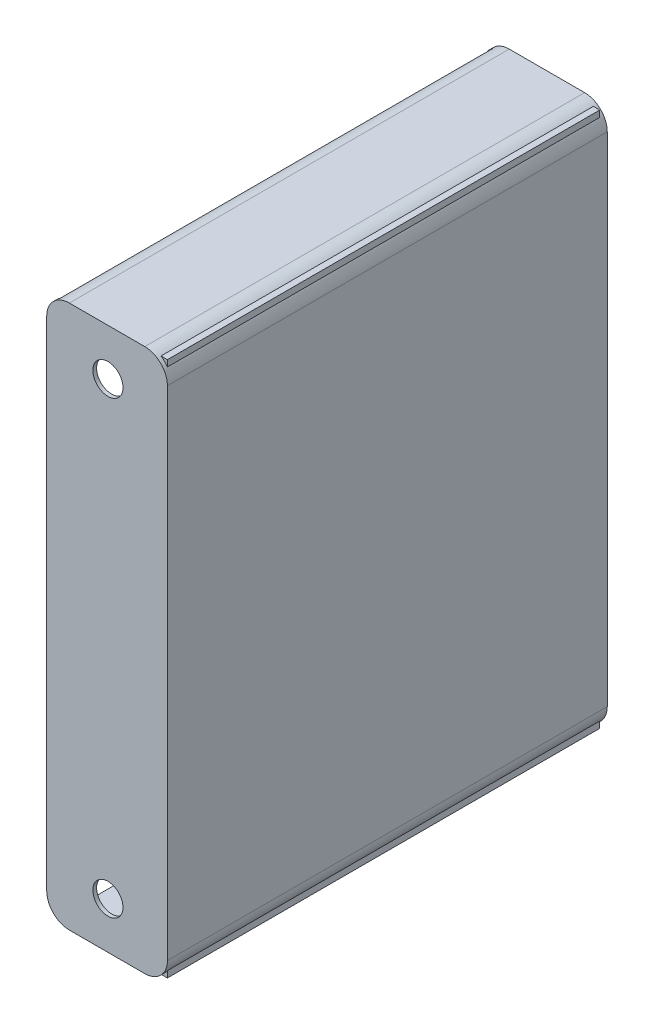
SolidWorks part; units mm, degrees
material "Hexcel AS4C (3000 Filaments)"
ref_plane "Front Plane" through (0, 0, 0) normal (0, 0, 1) x (1, 0, 0)
ref_plane "Top Plane" through (0, 0, 0) normal (0, 1, 0) x (1, 0, 0)
ref_plane "Right Plane" through (0, 0, 0) normal (1, 0, 0) x (0, 0, -1)
sketch "Sketch1" plane through (0, 0, 0) normal (1, 0, 0) x (0, 0, -1)
  line L1 (370.332, -457.2) -> (-370.332, -457.2)
  line L2 (370.332, -457.2) -> (370.332, 457.2)
  line L3 (370.332, 457.2) -> (-370.332, 457.2)
  line L4 (-370.332, -457.2) -> (-370.332, 457.2)
  line L5 (370.332, -457.2) -> (-370.332, 457.2) construction
  line L6 (370.332, 457.2) -> (-370.332, -457.2) construction
  point P0 (0, 0)
  dimension "D1" = 740.664
  dimension "D2" = 914.4
extrude "Boss-Extrude1" add sketch "Sketch1" along normal blind 203.2
shell "Shell1" thickness 6.35 removed face at (0, 0, 0)
sketch "Sketch4" plane through (0, 0, 370.332) normal (0, 0, 1) x (1, 0, 0)
  circle A0 centre (103.0428, 378.9942) radius 25.4
  dimension "D1" = 50.8
  dimension "D2" = 378.9942
  dimension "D3" = 103.0428
extrude "Cut-Extrude1" cut sketch "Sketch4" against normal blind 853.694
mirror "Mirror1" about plane through (0, 0, 0) normal (0, 1, 0) of "Cut-Extrude1"
fillet "Fillet1" radius 38.1 4 edges at (203.2, -457.2, 0) (0, -457.2, 0) (203.2, 457.2, 0) (0, 457.2, 0)
scale "Scale1" scale about centroid uniform scaling yes scale factor 0.5867
